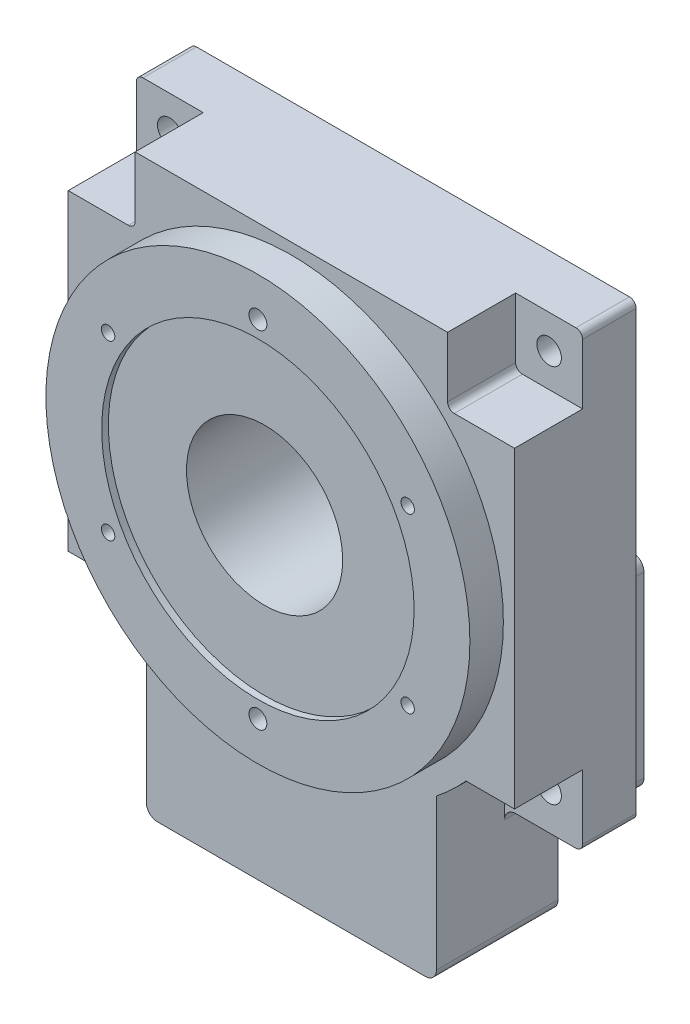
SolidWorks part; units mm, degrees
note: The reader was unsure of these and kept them because the rebuilt part matched: shared geometry of "草图1<3>", "草图1<4>", "草图1<5>", "草图2<3>", "草图2<4>", "草图4<3>".
material "45#"
ref_plane "前视基准面" through (0, 0, 0) normal (0, 0, 1) x (1, 0, 0)
ref_plane "上视基准面" through (0, 0, 0) normal (0, 1, 0) x (1, 0, 0)
ref_plane "右视基准面" through (0, 0, 0) normal (1, 0, 0) x (0, 0, -1)
sketch "草图1" plane through (0, 0, 0) normal (0, 0, 1) x (1, 0, 0)
  line L0 (0, 63.7634) -> (0, -57.3118) construction
  line L1 (-96.2366, 0) -> (90.4301, 0) construction
  line L2 (-100, 97) -> (-100, -99)
  line L3 (-97, -102) -> (97, -102)
  line L4 (-97, 100) -> (97, 100)
  line L5 (100, 97) -> (100, -99)
  line L6 (-65, -62.9833) -> (-65, -155)
  line L7 (-65, -155) -> (65, -155)
  line L8 (65, -62.9833) -> (65, -155)
  circle A0 centre (-85, 85) radius 5.5
  circle A1 centre (85, 85) radius 5.5
  circle A2 centre (-85, -85) radius 5.5
  circle A3 centre (0, 0) radius 95
  circle A4 centre (85, -85) radius 5.5
  arc A5 (-32.0156, 100) -> (-100, 32.0156) centre (0, 0) ccw
  circle A6 centre (0, 0) radius 35
  circle A7 centre (0, 0) radius 70
  circle A8 centre (0, 0) radius 77.5 construction
  circle A9 centre (0, 77.5) radius 3
  circle A10 centre (67.117, 38.75) radius 3
  circle A11 centre (67.117, -38.75) radius 3
  circle A12 centre (0, -77.5) radius 3
  circle A13 centre (-67.117, -38.75) radius 3
  circle A14 centre (-67.117, 38.75) radius 3
  circle A17 centre (-7, -101) radius 1.25
  circle A18 centre (7, -101) radius 1.25
  arc A19 (-100, -32.0156) -> (-65, -82.4621) centre (0, 0) ccw
  arc A20 (100, 32.0156) -> (32.0156, 100) centre (0, 0) ccw
  arc A21 (65, -82.4621) -> (100, -32.0156) centre (0, 0) ccw
  circle A22 centre (0, 77.5) radius 4
  circle A23 centre (0, -77.5) radius 4
  arc A34 (100, -99) -> (97, -102) centre (97, -99) cw
  arc A35 (-100, -99) -> (-97, -102) centre (-97, -99) ccw
  arc A36 (100, 97) -> (97, 100) centre (97, 97) ccw
  arc A37 (-100, 97) -> (-97, 100) centre (-97, 97) cw
  point P37 (0, 0)
  point P44 (0, -155)
  point P49 (25, 25)
  point P50 (-21.25, 25)
  point P51 (-25, 25)
  point P53 (-25, -25)
  point P55 (25, -25)
  point P62 (29, 25)
  point P66 (28.75, -25)
  point P69 (-21, -25)
  point P79 (100, -102)
  point P82 (-100, -102)
  point P85 (100, 100)
  point P88 (-100, 100)
  dimension "D3" = 11
  dimension "D4" = 11
  dimension "D5" = 170
  dimension "D6" = 170
  dimension "D7" = 70
  dimension "D8" = 100
  dimension "D9" = 190
  dimension "D10" = 140
  dimension "D11" = 155
  dimension "D12" = 6
  dimension "D15" = 255
  dimension "D17" = 14
  dimension "D20" = 2.5
  dimension "D22" = 3
  dimension "D21" = 210
  dimension "D24" = 8
  dimension "D25" = 8
  dimension "D16" = 130
  dimension "D18" = 200
  dimension "D19" = 102
  dimension "D23" = 101
  dimension "D13" = 6
extrude "凸台-拉伸1" add sketch "草图1" along normal blind 54.5
extrude "凸台-拉伸2" add sketch "草图1<3>" along normal blind 24
sketch "草图1<3>" plane through (0, 0, 0) normal (0, 0, 1) x (1, 0, 0) same geometry as "草图1"
extrude "凸台-拉伸3" add sketch "草图1<4>" along normal blind 15 from vertex at 54.5
sketch "草图1<4>" plane through (0, 0, 0) normal (0, 0, 1) x (1, 0, 0) same geometry as "草图1"
extrude "切除-拉伸1" cut sketch "草图1<5>" against normal blind 3 from offset 69.5 contours A7 A6
sketch "草图1<5>" plane through (0, 0, 0) normal (0, 0, 1) x (1, 0, 0) same geometry as "草图1"
sketch "草图2" plane through (0, 0, 0) normal (0, 0, 1) x (1, 0, 0)
  line L0 (0, 0) -> (0, -204) construction
  line L2 (-40, -57) -> (40, -57)
  line L3 (-45, -62) -> (-45, -142)
  line L4 (-40, -147) -> (40, -147)
  line L5 (45, -62) -> (45, -142)
  line L6 (-34.7897, -67.2103) -> (0, -102) construction
  line L8 (0, -102) -> (41.208, -102) construction
  circle A0 centre (0, -102) radius 49.2 construction
  circle A1 centre (-34.7897, -67.2103) radius 3
  circle A2 centre (34.7897, -67.2103) radius 3
  circle A3 centre (34.7897, -136.7897) radius 3
  circle A4 centre (-34.7897, -136.7897) radius 3
  circle A5 centre (0, -102) radius 9.5
  arc A6 (-45, -142) -> (-40, -147) centre (-40, -142) ccw
  arc A7 (40, -147) -> (45, -142) centre (40, -142) ccw
  arc A8 (-40, -57) -> (-45, -62) centre (-40, -62) ccw
  arc A9 (40, -57) -> (45, -62) centre (40, -62) cw
  point P3 (0, -102)
  point P24 (0, -102)
  dimension "D3" = 98.4
  dimension "D4" = 6
  dimension "D5" = 4
  dimension "D6" = 19
  dimension "D7" = 5
  dimension "D9" = 45
  dimension "D1" = 90
  dimension "D2" = 102
  dimension "D8" = 90
  dimension "D10" = 45
extrude "凸台-拉伸4" add sketch "草图2" against normal blind 58.5 contours A2 | A5 | A9 L2 A8 L3 A6 L4 A7 L5 A5 A4 A3 A2 A1 | A1 | A4 | A3
extrude "切除-拉伸2" cut sketch "草图2<3>" along normal blind 41 from vertex at -58.5 contours A5 starting at point (-45, -62, -58.5)
sketch "草图2<3>" plane through (0, 0, 0) normal (0, 0, 1) x (1, 0, 0) same geometry as "草图2"
extrude "切除-拉伸3" cut sketch "草图2<4>" along normal blind 15 from vertex at -58.5 contours A2 | A1 | A3 | A4 starting at point (-45, -62, -58.5)
sketch "草图2<4>" plane through (0, 0, 0) normal (0, 0, 1) x (1, 0, 0) same geometry as "草图2"
fillet "圆角1" radius 5 4 edges at (-65, -102, 12) (65, -102, 12) (-65, -155, 27.25) (65, -155, 27.25)
sketch "草图3" plane through (0, 0, -58.5) normal (0, 0, -1) x (-1, 0, 0)
  circle A0 centre (0, -102) radius 25
  dimension "D1" = 50
extrude "切除-拉伸4" cut sketch "草图3" against normal blind 3
sketch "草图4" plane through (0, 0, 54.5) normal (0, 0, 1) x (1, 0, 0)
  line L0 (-152.1175, 0) -> (142.9867, 0) construction
  line L1 (-73, 70) -> (-100, 70)
  line L2 (-70, 73) -> (-70, 100)
  line L3 (-70, 100) -> (-100, 100)
  line L4 (-100, 70) -> (-100, 100)
  line L5 (0, 128.9273) -> (0, -111.5725) construction
  line L6 (-100, 97) -> (-100, -32.0156) construction
  line L7 (-97, 100) -> (97, 100) construction
  line L8 (100, 70) -> (100, 100)
  line L9 (70, 100) -> (100, 100)
  line L10 (70, 73) -> (70, 100)
  line L11 (73, 70) -> (100, 70)
  line L12 (73, -70) -> (100, -70)
  line L13 (70, -73) -> (70, -100)
  line L14 (70, -100) -> (100, -100)
  line L15 (100, -70) -> (100, -100)
  line L16 (-100, -70) -> (-100, -100)
  line L17 (-70, -100) -> (-100, -100)
  line L18 (-70, -73) -> (-70, -100)
  line L19 (-73, -70) -> (-100, -70)
  line L20 (-100, -70) -> (-100, -25.2472)
  line L21 (-100, -25.2472) -> (-70.8787, -70.8787)
  line L22 (100, -70) -> (100, -25.2472)
  line L23 (100, 97) -> (100, -32.0156) construction
  line L24 (100, -25.2472) -> (70.8787, -70.8787)
  arc A0 (-73, 70) -> (-70, 73) centre (-73, 73) ccw
  arc A1 (73, 70) -> (70, 73) centre (73, 73) cw
  arc A2 (73, -70) -> (70, -73) centre (73, -73) ccw
  arc A3 (-73, -70) -> (-70, -73) centre (-73, -73) cw
  circle M5 centre (85, 85) radius 5.5
  circle M6 centre (-85, 85) radius 5.5
  arc M12 (65, -82.4621) -> (100, -32.0156) centre (0, 0) ccw
  line M13 (100, -32.0156) -> (100, 97)
  arc M14 (100, 97) -> (97, 100) centre (97, 97) ccw
  line M15 (97, 100) -> (-97, 100)
  arc M16 (-97, 100) -> (-100, 97) centre (-97, 97) ccw
  line M17 (-100, 97) -> (-100, -32.0156)
  arc M18 (-100, -32.0156) -> (-65, -82.4621) centre (0, 0) ccw
  dimension "D3" = 3
  dimension "D1" = 30
  dimension "D2" = 30
extrude "凸台-拉伸5" add sketch "草图4" against normal up to next contours L20 L19 M18 | L12 L22 M12
extrude "切除-拉伸5" cut sketch "草图4<3>" against normal offset from surface (30.5 mm away) 24 contours L1 A0 L2 M15 M16 M17 M6 | A1 L11 L10 M13 M14 M15 M5 up to face at (90.5, -85, 0)
sketch "草图4<3>" plane through (0, 0, 54.5) normal (0, 0, 1) x (1, 0, 0) same geometry as "草图4"
